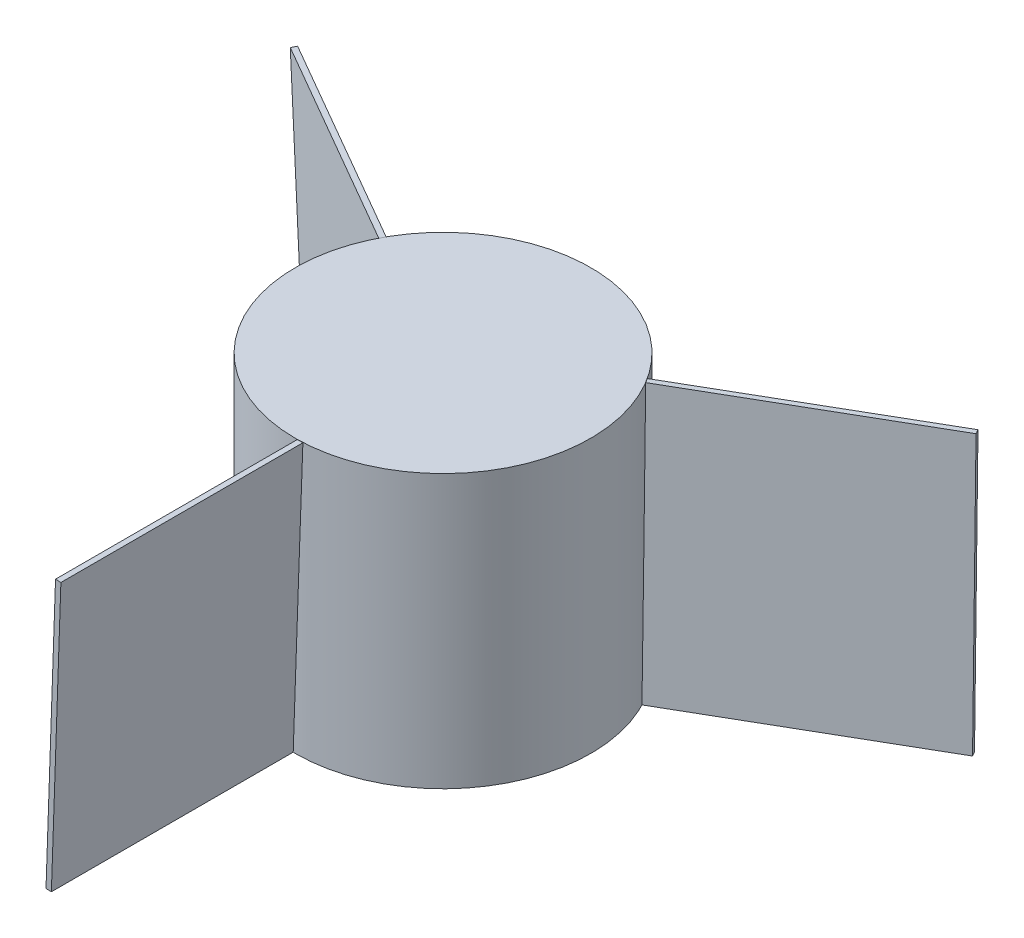
SolidWorks part; units mm, degrees
ref_plane "Front Plane" through (0, 0, 0) normal (0, 0, 1) x (1, 0, 0)
ref_plane "Top Plane" through (0, 0, 0) normal (0, 1, 0) x (1, 0, 0)
ref_plane "Right Plane" through (0, 0, 0) normal (1, 0, 0) x (0, 0, -1)
sketch "Sketch1" plane through (0, 0, 0) normal (0, 1, 0) x (1, 0, 0)
  circle A0 centre (0, 0) radius 82.5
  dimension "D1" = 165
extrude "Boss-Extrude1" add sketch "Sketch1" along normal blind 152.4
sketch "Sketch2" plane through (0, 0, 0) normal (1, 0, 0) x (0, 0, -1)
  line L0 (-135.2989, 76.2) -> (106.0289, 76.2) construction
  line L1 (-82.5, 0) -> (82.5, 0) construction
  line L2 (82.5, 152.4) -> (-82.5, 152.4) construction
  point P3 (0, 0)
  point P8 (-135.2989, 76.2)
  point P9 (0, 0)
ref_plane "Plane1" through (-2.6577, 0.0928, 0) normal (0.9994, -0.0349, 0) x (0, 0, -1)
ref_axis "Axis1" through (0, 152.4, 0) along (0, -1, 0)
sketch "Sketch3" plane through (-2.6577, 0.0928, 0) normal (0.9994, -0.0349, 0) x (0, 0, -1)
  line L1 (0, 0) -> (-217.5, 0)
  line L2 (0, 0) -> (0, 152.3072)
  line L3 (0, 152.3072) -> (-217.5, 152.3072)
  line L4 (-217.5, 0) -> (-217.5, 152.3072)
  line L5 (0, 152.3072) -> (0, 0) construction
  point P5 (0, 0)
  point P6 (0, 0)
  point P7 (-82.5, 142.6764)
  point P8 (-81.5904, -24.1263)
  point P11 (0, -19.6468)
  point P12 (-217.5, 181.9577)
  point P13 (0, 173.5802)
  point P14 (0, 0)
  point P15 (0, 148.5383)
  point P18 (0, 0)
  dimension "D1" = 217.5
extrude "Boss-Extrude2" add sketch "Sketch3" along normal mid plane 3
pattern_circular "CirPattern1" count 3 over 360 about axis through (0, 152.4, 0) along (0, -1, 0) of "Boss-Extrude2"
